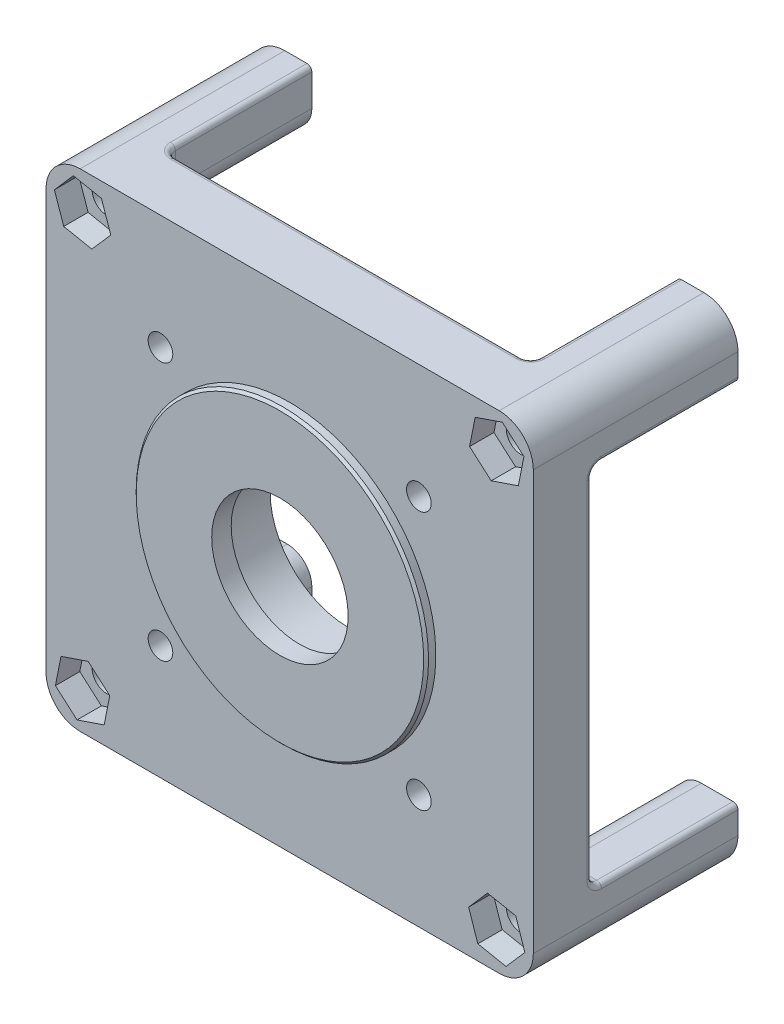
SolidWorks part; units mm, degrees
note: '?' marks a value the reader was unsure of.
ref_plane "Front Plane" through (0, 0, 0) normal (0, 0, 1) x (1, 0, 0)
ref_plane "Top Plane" through (0, 0, 0) normal (0, 1, 0) x (1, 0, 0)
ref_plane "Right Plane" through (0, 0, 0) normal (1, 0, 0) x (0, 0, -1)
ref_axis "Shaft Axis" through (0, 0, -0.635) along (0, 0, 1)?
sketch "Sketch2" plane through (0, 0, 0) normal (0, 0, 1) x (1, 0, 0)
  line L1 (-50, -50) -> (50, -50)
  line L2 (-50, -50) -> (-50, 50)
  line L3 (-50, 50) -> (50, 50)
  line L4 (50, -50) -> (50, 50)
  line L5 (-50, -50) -> (50, 50) construction
  line L6 (-50, 50) -> (50, -50) construction
  point P0 (0, 0)
  dimension "D1" = 100
extrude "Boss-Extrude1" add sketch "Sketch2" along normal blind 12
sketch "Sketch3" plane through (0, 0, 0) normal (0, 0, -1) x (-1, 0, 0)
  circle A0 centre (0, 0) radius 16
  dimension "D1" = 32
extrude "Cut-Extrude1" cut sketch "Sketch3" against normal blind 10
sketch "Sketch14" plane through (0, 0, 12) normal (0, 0, 1) x (1, 0, 0)
  circle A0 centre (0, 0) radius 65
  dimension "D1" = 130
extrude "Cut-Extrude2" [suppressed] cut sketch "Sketch14" against normal blind 2 flip side to cut
hole_wizard "7/16 Clearance Hole1" [suppressed] positions "Sketch7" profile "Sketch8" hole size "7/16" standard "ANSI Inch"
sketch "Sketch7" [suppressed] plane through (0, 0, 10.7) normal (0, 0, 1) x (1, 0, 0)
  line L1 (-58.7375, -58.7375) -> (58.7375, -58.7375) construction
  line L2 (-58.7375, -58.7375) -> (-58.7375, 58.7375) construction
  line L3 (-58.7375, 58.7375) -> (58.7375, 58.7375) construction
  line L4 (58.7375, -58.7375) -> (58.7375, 58.7375) construction
  line L5 (-58.7375, -58.7375) -> (58.7375, 58.7375) construction
  line L6 (-58.7375, 58.7375) -> (58.7375, -58.7375) construction
  line L7 (-76.2, 76.2) -> (76.2, -76.2) construction
  line L8 (76.2, -76.2) -> (76.2, 76.2) construction
  line L9 (76.2, 76.2) -> (-76.2, -76.2) construction
  point P2 (58.7375, 58.7375)
  point P35 (-58.7375, -58.7375)
  point P36 (-58.7375, 58.7375)
  point P37 (58.7375, -58.7375)
  dimension "D1" = 117.475
sketch "Sketch8" plane through (58.7375, 58.7375, 10.7) normal (1, 0, 0) x (0, -1, 0)
  line L0 (0, 0) -> (0, 10.7)
  line L1 (0, 10.7) -> (6.1519, 10.7)
  line L2 (6.1519, 10.7) -> (6.1519, 0)
  line L5 (6.1519, 0) -> (0, 0)
  line L11 (0, -6.35) -> (0, 107.95) construction
  dimension "Thru Hole Dia." = 12.3038
  dimension "Thru Hole Depth" = 10.7
hole_wizard "M6 Clearance Hole1" positions "Sketch13" profile "Sketch12" hole size "M6" standard "ANSI Metric" end condition through all
sketch "Sketch13" plane through (0, 0, 12) normal (0, 0, -1) x (-1, 0, 0)
  line L1 (-42.5, -42.5) -> (42.5, -42.5) construction
  line L2 (-42.5, -42.5) -> (-42.5, 42.5) construction
  line L3 (-42.5, 42.5) -> (42.5, 42.5) construction
  line L4 (42.5, -42.5) -> (42.5, 42.5) construction
  line L5 (-42.5, -42.5) -> (42.5, 42.5) construction
  line L6 (-42.5, 42.5) -> (42.5, -42.5) construction
  line L22 (50, -50) -> (50, 50)
  line L24 (50, 50) -> (-50, -50) construction
  line L26 (-50, 50) -> (50, -50) construction
  line L43 (-50, 50) -> (-50, -50)
  line L44 (-50, 50) -> (-50, -50)
  line L45 (50, 50) -> (-50, 50)
  line L46 (50, 50) -> (-50, 50)
  line L47 (50, -50) -> (50, 50)
  line L48 (50, -50) -> (50, 50)
  line L49 (-50, -50) -> (50, -50)
  line L50 (-50, -50) -> (50, -50)
  point P2 (42.5, 42.5)
  point P61 (-42.5, -42.5)
  point P62 (-42.5, 42.5)
  point P63 (42.5, -42.5)
  dimension "D1" = 85
  dimension "D2" = 0
sketch "Sketch12" plane through (-42.5, 42.5, 12) normal (1, 0, 0) x (0, -1, 0)
  line L0 (0, 0) -> (0, 12)
  line L1 (0, 12) -> (3.05, 12)
  line L2 (3.05, 12) -> (3.05, 0)
  line L5 (3.05, 0) -> (0, 0)
  line L11 (0, -6.35) -> (0, 107.95) construction
  dimension "Thru Hole Dia." = 6.1
  dimension "Thru Hole Depth" = 12
sketch "Sketch17" plane through (0, 0, 0) normal (0, 0, -1) x (-1, 0, 0)
  line L0 (-37.45, 42.5) -> (-37.45, 50)
  line L1 (-50, 50) -> (50, 50) construction
  line L2 (-37.45, 50) -> (-50, 50)
  line L3 (-50, 50) -> (-50, 37.45)
  line L4 (-50, -50) -> (-50, 50) construction
  line L5 (-50, 37.45) -> (-42.5, 37.45)
  arc A0 (-42.5, 37.45) -> (-37.45, 42.5) centre (-42.5, 42.5) ccw
  circle A1 centre (-42.5, 42.5) radius 3.05 construction
  circle A2 centre (-42.5, 42.5) radius 3.05
  dimension "D1" = 2
extrude "Boss-Extrude2" add sketch "Sketch17" along normal blind 30
pattern_circular "CirPattern1" count 4 over 360 about axis through (0, 0, 0) along (0, 0, 1) of "Boss-Extrude2"
sketch "Sketch18" plane through (0, 0, 0) normal (0, 0, -1) x (-1, 0, 0)
  circle A0 centre (0, 0) radius 14
  dimension "D1" = 28
extrude "Cut-Extrude3" cut sketch "Sketch18" against normal through all
fillet "Fillet1" radius 2 12 edges at (38.9291, 38.9291, 0) (-38.9291, 38.9291, 0) (-38.9291, -38.9291, 0) (38.9291, -38.9291, 0) (-37.45, 46.25, 0) (-46.25, 37.45, 0) (-46.25, -37.45, 0) (-37.45, -46.25, 0) (37.45, -46.25, 0) (46.25, -37.45, 0) (46.25, 37.45, 0) (37.45, 46.25, 0)
fillet "Fillet2" radius 7 4 edges at (-50, -50, -9) (50, -50, -9) (50, 50, -9) (-50, 50, -9)
sketch "Sketch24" plane through (0, 0, 12) normal (0, 0, 1) x (1, 0, 0)
  line L1 (-44.4006, 48.0738) -> (-48.2774, 43.6409)
  line L2 (-48.2774, 43.6409) -> (-46.3768, 38.0671)
  line L3 (-46.3768, 38.0671) -> (-40.5994, 36.9262)
  line L4 (-40.5994, 36.9262) -> (-36.7226, 41.3591)
  line L5 (-36.7226, 41.3591) -> (-38.6232, 46.9329)
  line L6 (-38.6232, 46.9329) -> (-44.4006, 48.0738)
  circle A0 centre (-42.5, 42.5) radius 5.1 construction
  dimension "D1" = 10.2
extrude "Cut-Extrude6" cut sketch "Sketch24" against normal blind 5
pattern_circular "CirPattern2" count 4 over 360 about axis through (0, 0, 0) along (0, 0, 1) of "Cut-Extrude6"
sketch "Sketch25" plane through (0, 0, 12) normal (0, 0, 1) x (1, 0, 0)
  circle A0 centre (0, 0) radius 14
  circle A1 centre (0, 0) radius 30
  circle A2 centre (0, 0) radius 14 construction
  dimension "D1" = 60
extrude "Boss-Extrude3" add sketch "Sketch25" along normal blind 2
sketch "Sketch26" plane through (0, 0, 12) normal (0, 0, 1) x (1, 0, 0)
  line L1 (-26.5165, 26.5165) -> (26.5165, 26.5165)
  line L2 (-26.5165, 26.5165) -> (-26.5165, -26.5165)
  line L3 (-26.5165, -26.5165) -> (26.5165, -26.5165)
  line L4 (26.5165, 26.5165) -> (26.5165, -26.5165)
  line L5 (-26.5165, 26.5165) -> (26.5165, -26.5165) construction
  line L6 (-26.5165, -26.5165) -> (26.5165, 26.5165) construction
  point P0 (0, 0)
  dimension "D1" = 75
  dimension "D2" = 45
hole_wizard "#8 (0.199) Diameter Hole1" positions "3DSketch1" profile "Sketch27" hole size "#8" standard "ANSI Inch" end condition up to next
sketch3d "3DSketch1"
  point P0 (26.5165, 26.5165, 12)
  point P3 (-26.5165, 26.5165, 12)
  point P6 (-26.5165, -26.5165, 12)
  point P9 (26.5165, -26.5165, 12)
sketch "Sketch27" plane through (26.5165, 26.5165, 12) normal (1, 0, 0) x (0, -1, 0)
  line L0 (0, 0) -> (0, 12)
  line L1 (0, 12) -> (2.5273, 12)
  line L2 (2.5273, 12) -> (2.5273, 0)
  line L5 (2.5273, 0) -> (0, 0)
  line L11 (0, -6.35) -> (0, 107.95) construction
  dimension "Thru Hole Dia." = 5.0546
  dimension "Thru Hole Depth" = 12
chamfer "Chamfer1" distance 0.5 angle 45 1 edges at (30, 0, 14)
fillet "Fillet3" radius 1 20 edges at (50, 0, 0) (0, -50, 0) (-50, 0, 0) (0, 50, 0) (-36.8642, 50, -0.5858) (-50, 36.8642, -0.5858) (-50, -36.8642, -0.5858) (-36.8642, -50, -0.5858) (36.8642, -50, -0.5858) (50, -36.8642, -0.5858) (50, 36.8642, -0.5858) (36.8642, 50, -0.5858) (37.45, 50, -16) (50, 37.45, -16) (-50, 37.45, -16) (-37.45, 50, -16) (-37.45, -50, -16) (-50, -37.45, -16) (50, -37.45, -16) (37.45, -50, -16)
